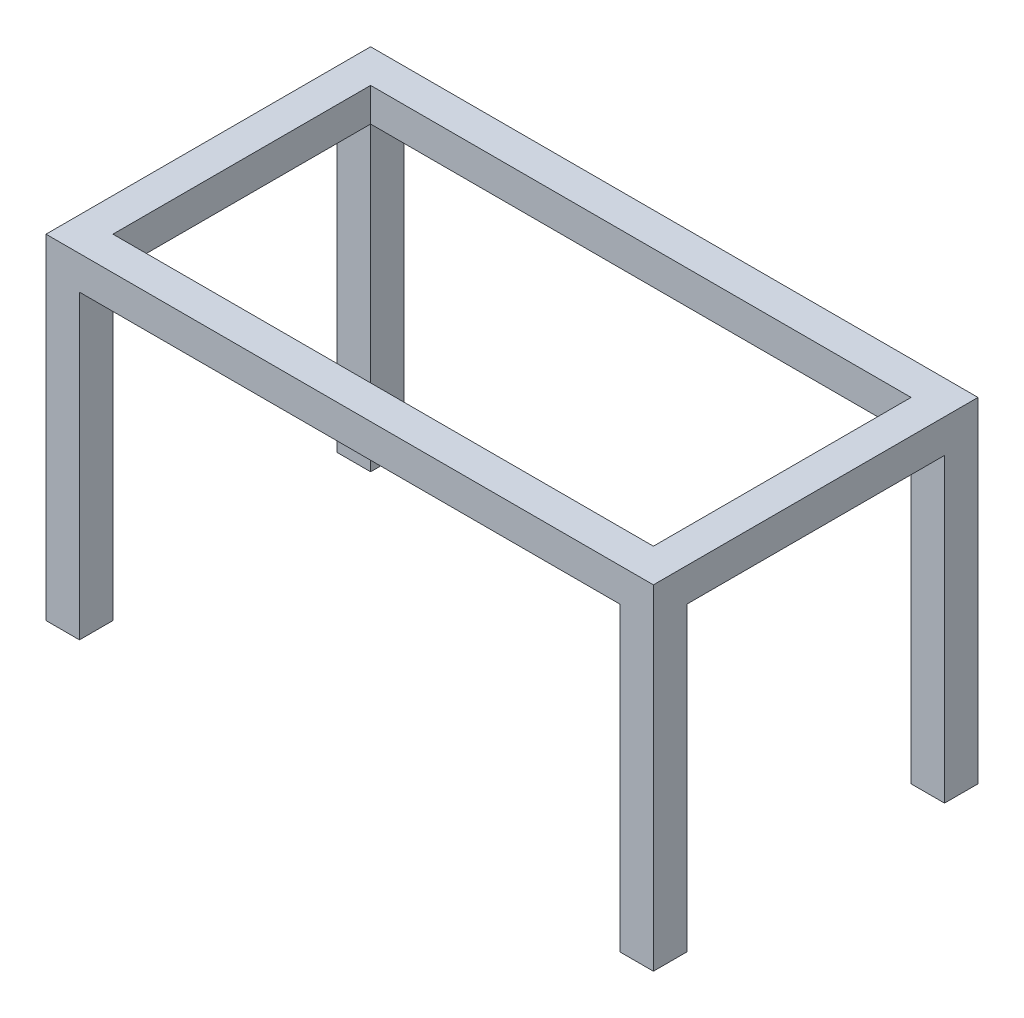
SolidWorks part; units mm, degrees
ref_plane "Front Plane" through (0, 0, 0) normal (0, 0, 1) x (1, 0, 0)
ref_plane "Top Plane" through (0, 0, 0) normal (0, 1, 0) x (1, 0, 0)
ref_plane "Right Plane" through (0, 0, 0) normal (1, 0, 0) x (0, 0, -1)
sketch "Sketch1" plane through (0, 0, 0) normal (0, 1, 0) x (1, 0, 0)
  line L1 (-40.375, -19.25) -> (40.375, -19.25) construction
  line L2 (-40.375, -19.25) -> (-40.375, 19.25) construction
  line L3 (-40.375, 19.25) -> (40.375, 19.25) construction
  line L4 (40.375, -19.25) -> (40.375, 19.25) construction
  line L5 (-40.375, -19.25) -> (40.375, 19.25) construction
  line L6 (-40.375, 19.25) -> (40.375, -19.25) construction
  line L7 (-40.375, 19.25) -> (-45.375, 19.25)
  line L8 (-40.375, 19.25) -> (-40.375, 24.25)
  line L9 (-40.375, 24.25) -> (-45.375, 24.25)
  line L10 (-45.375, 19.25) -> (-45.375, 24.25)
  line L11 (-40.375, -19.25) -> (-45.375, -19.25)
  line L12 (-40.375, -19.25) -> (-40.375, -24.25)
  line L13 (-40.375, -24.25) -> (-45.375, -24.25)
  line L14 (-45.375, -19.25) -> (-45.375, -24.25)
  line L15 (40.375, 19.25) -> (45.375, 19.25)
  line L16 (40.375, 19.25) -> (40.375, 24.25)
  line L17 (40.375, 24.25) -> (45.375, 24.25)
  line L18 (45.375, 19.25) -> (45.375, 24.25)
  line L19 (40.375, -19.25) -> (45.375, -19.25)
  line L20 (40.375, -19.25) -> (40.375, -24.25)
  line L21 (40.375, -24.25) -> (45.375, -24.25)
  line L22 (45.375, -19.25) -> (45.375, -24.25)
  point P0 (0, 0)
  dimension "D1" = 80.75
  dimension "D2" = 38.5
  dimension "D3" = 5
  dimension "D4" = 5
  dimension "D5" = 5
  dimension "D6" = 5
extrude "Boss-Extrude1" add sketch "Sketch1" along normal blind 50
sketch "Sketch2" plane through (-40.375, 0, 0) normal (1, 0, 0) x (0, 0, -1)
  line L0 (24.25, 50) -> (24.25, 0) construction
  line L1 (19.25, 50) -> (24.25, 50)
  line L2 (19.25, 50) -> (19.25, 45)
  line L3 (19.25, 45) -> (24.25, 45)
  line L4 (24.25, 50) -> (24.25, 45)
  line L5 (-19.25, 50) -> (-19.25, 0) construction
  line L6 (-24.25, 50) -> (-19.25, 50)
  line L7 (-24.25, 50) -> (-24.25, 45)
  line L8 (-24.25, 45) -> (-19.25, 45)
  line L9 (-19.25, 50) -> (-19.25, 45)
  dimension "D1" = 5
extrude "Boss-Extrude2" add sketch "Sketch2" along normal up to next (80.75 mm away)
sketch "Sketch3" plane through (0, 0, -19.25) normal (0, 0, 1) x (1, 0, 0)
  line L1 (-45.375, 50) -> (-40.375, 50)
  line L2 (-45.375, 50) -> (-45.375, 45)
  line L3 (-45.375, 45) -> (-40.375, 45)
  line L4 (-40.375, 50) -> (-40.375, 45)
  line L5 (40.375, 45) -> (45.375, 45)
  line L6 (40.375, 45) -> (40.375, 50)
  line L7 (40.375, 50) -> (45.375, 50)
  line L8 (45.375, 45) -> (45.375, 50)
extrude "Boss-Extrude3" add sketch "Sketch3" along normal up to next (38.5 mm away)
